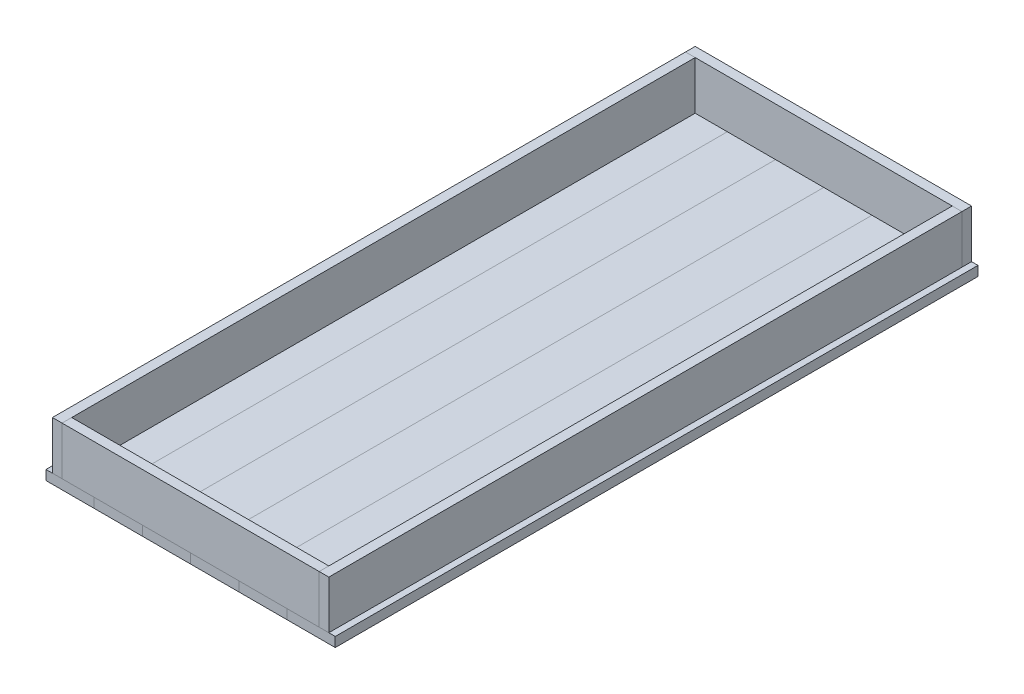
SolidWorks part; units mm, degrees
material "Pine"
ref_plane "Piano frontale" through (0, 0, 0) normal (0, 0, 1) x (1, 0, 0)
ref_plane "Piano superiore" through (0, 0, 0) normal (0, 1, 0) x (1, 0, 0)
ref_plane "Piano destro" through (0, 0, 0) normal (1, 0, 0) x (0, 0, -1)
sketch "Sketch4" plane through (0, 0, 0) normal (1, 0, 0) x (0, 0, -1)
  line L1 (0, 0) -> (100, 0)
  line L2 (0, 0) -> (0, 1.5)
  line L3 (0, 1.5) -> (100, 1.5)
  line L4 (100, 0) -> (100, 1.5)
  dimension "D1" = 100
  dimension "D2" = 1.5
extrude "Boss-Extrude3" add sketch "Sketch4" against normal blind 7.5
extrude "Boss-Extrude4" add sketch "Sketch4<2>" against normal blind 7.5 from offset 7.5 separate body offset against normal yes
sketch "Sketch4<2>" plane through (0, 0, 0) normal (1, 0, 0) x (0, 0, -1) same geometry as "Sketch4"
pattern_linear "LPattern7" count 5 spacing 7.5 along (-1, 0, 0) of "Boss-Extrude4"
sketch "Sketch5" plane through (0, 0, 0) normal (0, 0, 1) x (1, 0, 0)
  line L0 (-45, 1.5) -> (-37.5, 1.5) construction
  line L1 (-44, 1.5) -> (-1, 1.5)
  line L2 (-44, 1.5) -> (-44, 9)
  line L3 (-44, 9) -> (-1, 9)
  line L4 (-1, 1.5) -> (-1, 9)
  line L5 (-45, 1.5) -> (-45, 0) construction
  line L6 (0, 1.5) -> (0, 0) construction
  dimension "D1" = 1
  dimension "D2" = 1
  dimension "D3" = 7.5
extrude "Boss-Extrude5" add sketch "Sketch5" along normal blind 1.5 from offset 100 separate body offset against normal yes
sketch "Sketch6" plane through (0, 0, 0) normal (1, 0, 0) x (0, 0, -1)
  line L0 (100, 1.5) -> (0, 1.5) construction
  line L1 (0, 1.5) -> (98.5, 1.5)
  line L2 (0, 1.5) -> (0, 9)
  line L3 (0, 9) -> (98.5, 9)
  line L4 (98.5, 1.5) -> (98.5, 9)
  line L6 (0, 1.5) -> (0, 0) construction
extrude "Boss-Extrude7" add sketch "Sketch6" against normal blind 1.5 from offset 1 separate body offset against normal yes
extrude "Boss-Extrude8" add sketch "Sketch6<3>" along normal blind 1.5 from offset 44 separate body offset against normal yes
sketch "Sketch6<3>" plane through (0, 0, 0) normal (1, 0, 0) x (0, 0, -1) same geometry as "Sketch6"
sketch "Sketch7" plane through (0, 0, 0) normal (0, 0, 1) x (1, 0, 0)
  line L1 (-42.5, 9) -> (-2.5, 9)
  line L2 (-42.5, 9) -> (-42.5, 1.5)
  line L3 (-42.5, 1.5) -> (-2.5, 1.5)
  line L4 (-2.5, 9) -> (-2.5, 1.5)
extrude "Boss-Extrude10" add sketch "Sketch7" against normal blind 1.5 separate body
scale "Scale2" bodies to scale 114 117 116 118 105 104 110 111 112 113 scale about origin uniform scaling yes scale factor 10
